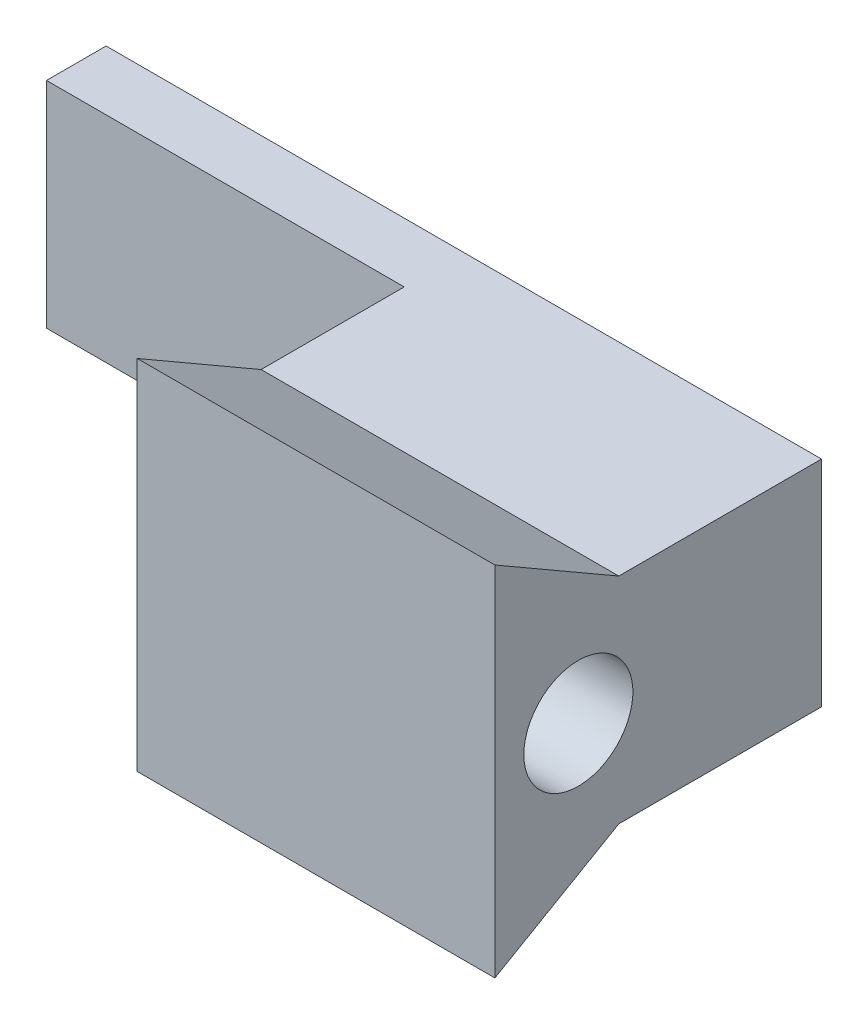
SolidWorks part; units mm, degrees
material "Polyetheretherketone (PEEK)"
ref_plane "Front Plane" through (0, 0, 0) normal (0, 0, 1) x (1, 0, 0)
ref_plane "Top Plane" through (0, 0, 0) normal (0, 1, 0) x (1, 0, 0)
ref_plane "Right Plane" through (0, 0, 0) normal (1, 0, 0) x (0, 0, -1)
sketch "Sketch1" plane through (0, 0, 0) normal (1, 0, 0) x (0, 0, -1)
  line L0 (0, -1.5) -> (0, 1.5)
  line L1 (0, 1.5) -> (1.0392, 0.9)
  line L2 (1.0392, -0.9) -> (2.2392, -0.9)
  line L4 (2.7392, 0.9) -> (2.7392, -0.9)
  line L5 (2.7392, -0.9) -> (2.2392, -0.9)
  line L7 (1.0392, -0.9) -> (0, -1.5)
  line L8 (1.0392, 0.9) -> (2.2392, 0.9)
  line L11 (2.7392, -0.9) -> (2.2392, -0.9)
  line L12 (2.7392, -0.9) -> (2.7392, 0.9)
  line L13 (2.7392, 0.9) -> (2.2392, 0.9)
  line L14 (2.2392, -0.9) -> (2.2392, 0.9)
  line L15 (2.7392, -0.9) -> (2.2392, 0.9) construction
  line L16 (2.7392, 0.9) -> (2.2392, -0.9) construction
  point P3 (0.7, 0)
  point P4 (0, 0)
  point P12 (2.7392, 0)
  point P13 (2.4892, 0)
  dimension "D1" = 3
  dimension "D2" = 60
  dimension "D3" = 60
  dimension "D4" = 1.8
  dimension "D6" = 1.2
  dimension "D7" = 1.8
  dimension "D8" = 0
  dimension "D9" = 0.7
  dimension "D10" = 0
  dimension "D11" = 0
  dimension "D13" = 1.8
  dimension "D5" = 0.5
  dimension "D12" = 1.2
extrude "Boss-Extrude1" add sketch "Sketch1" along normal blind 3 contours L8 L1 L0 L7 L2 | L5 L4 | L4 L11 L5 | L13 L4 region at (0, 0, -1.016) region at (0, 0, -2.4892)
hole_wizard "#00-90 Tapped Hole1" positions "Sketch2" profile "Sketch3" tap size "#00-90" standard "ANSI Inch" end condition through all
sketch "Sketch2" plane through (0, 0, 0) normal (-1, 0, 0) x (0, 0, 1)
  line L0 (0, -1.5) -> (0, 1.5) construction
  point P0 (-0.7, 0)
  dimension "D1" = 0.7
  dimension "D2" = 0
sketch "Sketch3" plane through (0, 0, -0.7) normal (0, 1, 0) x (0, 0, 1)
  line L0 (0, 0) -> (0, 3)
  line L1 (0, 3) -> (0.4572, 3)
  line L2 (0.4572, 3) -> (0.4572, 0)
  line L5 (0.4572, 0) -> (0, 0)
  line L11 (0, -6.35) -> (0, 107.95) construction
  dimension "Thru Tap Drill Dia." = 0.9144
  dimension "Thru Tap Drill Depth" = 3
cosmetic thread "Hole Thread1" parameters "D2"=1.1938
extrude "Boss-Extrude2" add sketch "Sketch1<5>" against normal blind 3 contours L14 L5 L4 L13 region at (0, 0, -2.4892)
sketch "Sketch1<5>" plane through (0, 0, 0) normal (1, 0, 0) x (0, 0, -1) same geometry as "Sketch1"
equation "\"D12@Sketch1\"=\"D6@Sketch1\""
